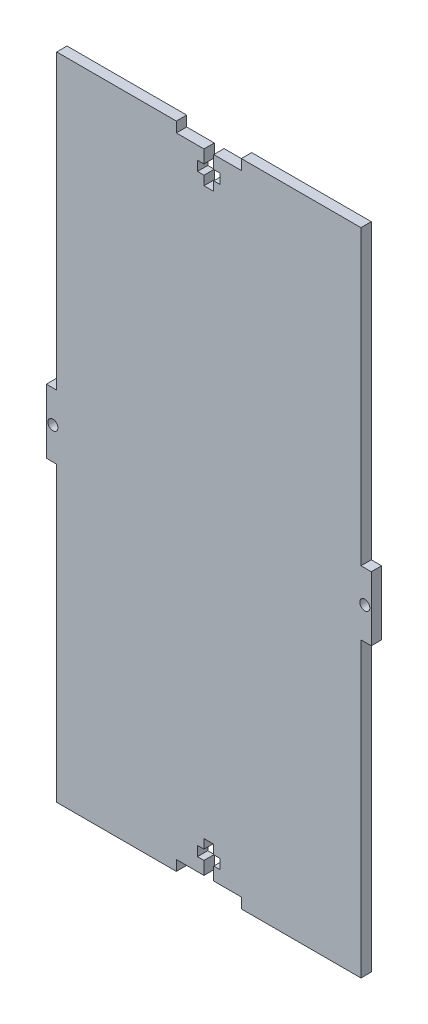
SolidWorks part; units mm, degrees
ref_plane "Front Plane" through (0, 0, 0) normal (0, 0, 1) x (1, 0, 0)
ref_plane "Top Plane" through (0, 0, 0) normal (0, 1, 0) x (1, 0, 0)
ref_plane "Right Plane" through (0, 0, 0) normal (1, 0, 0) x (0, 0, -1)
sketch "Sketch1" plane through (0, 0, 0) normal (0, 0, 1) x (1, 0, 0)
  line L0 (0, 40) -> (0, -40) construction
  line L5 (-50, -100) -> (50, 100) construction
  line L6 (-50, 100) -> (50, -100) construction
  line L7 (-100, 0) -> (100, 0) construction
  line L32 (-50, 100) -> (50, 100)
  line L35 (50, 100) -> (50, -100)
  line L36 (50, -100) -> (-50, -100)
  line L37 (-50, -100) -> (-50, 100)
  point P0 (0, 0)
  dimension "D1" = 100
  dimension "D2" = 200
extrude "Boss-Extrude2" add sketch "Sketch1" along normal blind 3.18
sketch "Sketch2" plane through (0, 0, 3.18) normal (0, 0, 1) x (1, 0, 0)
  line L0 (0, -100) -> (0, 100) construction
  line L1 (-123.0225, 0) -> (147.0753, 0) construction
  line L2 (50, 100) -> (-50, 100) construction
  line L4 (-10, 100) -> (-10, 96.82)
  line L5 (-10, 96.82) -> (-1.5, 96.82)
  line L6 (10, 100) -> (10, 96.82)
  line L7 (1.5, 96.82) -> (10, 96.82)
  line L9 (-1.5, 96.82) -> (-1.5, 92.82)
  line L10 (-1.5, 87) -> (1.5, 87)
  line L11 (1.5, 96.82) -> (1.5, 92.82)
  line L12 (-3.5, 92.82) -> (-1.5, 92.82)
  line L13 (-3.5, 92.82) -> (-3.5, 89.82)
  line L14 (-3.5, 89.82) -> (-1.5, 89.82)
  line L15 (3.5, 92.82) -> (3.5, 89.82)
  line L16 (1.5, 92.82) -> (3.5, 92.82)
  line L17 (-1.5, 89.82) -> (-1.5, 87)
  line L18 (1.5, 89.82) -> (1.5, 87)
  line L19 (1.5, 89.82) -> (3.5, 89.82)
  line L20 (-10, 100) -> (10, 100)
  line L21 (-50, -100) -> (50, -100) construction
  line L22 (-50, 100) -> (-50, -100) construction
  line L23 (-50, 9.875) -> (-46.82, 9.875)
  line L24 (-50, 9.875) -> (-50, 100)
  line L25 (-50, 100) -> (-46.82, 100)
  line L26 (-46.82, 9.875) -> (-46.82, 100)
  line L28 (-50, -9.875) -> (-46.82, -9.875)
  line L29 (-50, -9.875) -> (-50, -100)
  line L30 (-50, -100) -> (-46.82, -100)
  line L31 (-46.82, -9.875) -> (-46.82, -100)
  circle A0 centre (-48, 0) radius 1.55
  dimension "D11" = 3.1
  dimension "D12" = 2
  dimension "D1" = 4
  dimension "D2" = 3
  dimension "D3" = 3
  dimension "D4" = 20
  dimension "D5" = 7
  dimension "D6" = 3.18
  dimension "D7" = 13
  dimension "D8" = 19.75
  dimension "D9" = 3.18
  dimension "D10" = 3.18
extrude "Cut-Extrude1" cut sketch "Sketch2" against normal through all
mirror "Mirror1" about plane through (0, 0, 0) normal (0, 1, 0) of "Cut-Extrude1"
mirror "Mirror3" about plane through (0, 0, 0) normal (1, 0, 0) of "Cut-Extrude1"
